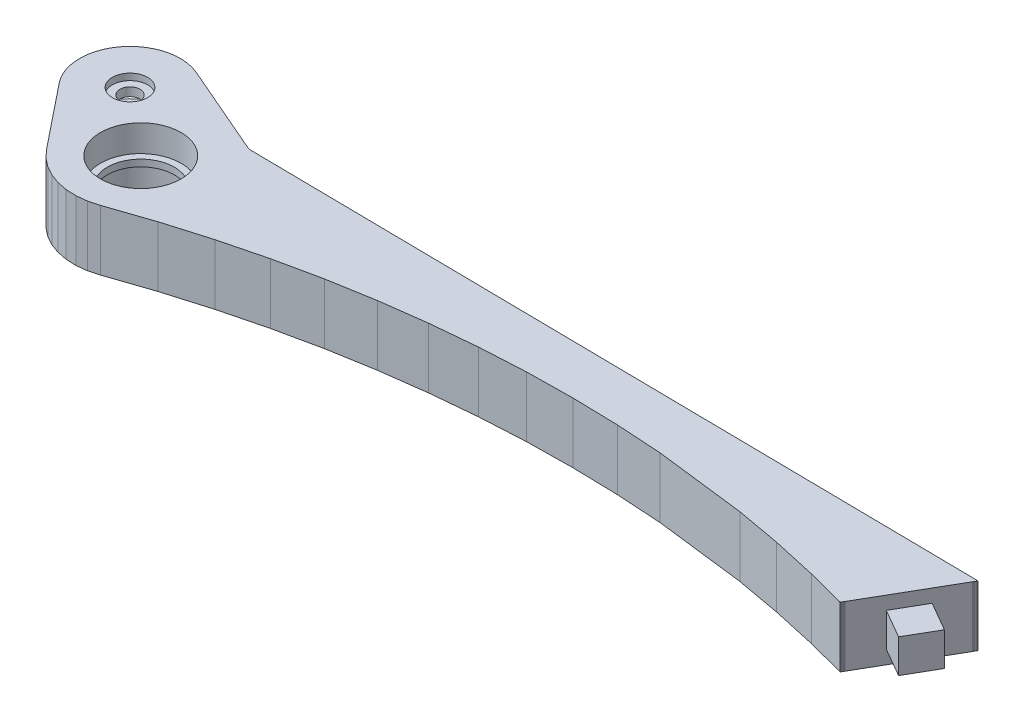
SolidWorks part; units mm, degrees
ref_plane "Спереди" through (0, 0, 0) normal (0, 0, 1) x (1, 0, 0)
ref_plane "Сверху" through (0, 0, 0) normal (0, 1, 0) x (1, 0, 0)
ref_plane "Справа" through (0, 0, 0) normal (1, 0, 0) x (0, 0, -1)
ref_plane "Плоскость4" through (0, 14.0561, 0) normal (0, 1, 0) x (1, 0, 0)
sketch "Эскиз49" plane through (0, 0, 0) normal (0, 1, 0) x (1, 0, 0)
  line L3 (268.0638, -16.9842) -> (254.1293, -41.1195)
  line L16 (268.6348, -15.9952) -> (268.6282, -16.0066)
  line L17 (268.6282, -16.0066) -> (268.6174, -16.0253)
  line L18 (268.6174, -16.0253) -> (268.6024, -16.0513)
  line L19 (268.6024, -16.0513) -> (268.5832, -16.0845)
  line L20 (268.5832, -16.0845) -> (268.5601, -16.1245)
  line L21 (268.5333, -16.171) -> (268.5601, -16.1245)
  line L22 (268.5333, -16.171) -> (268.5028, -16.2237)
  line L23 (268.5028, -16.2237) -> (268.4322, -16.3461)
  line L24 (268.4322, -16.3461) -> (268.3504, -16.4878)
  line L25 (268.3504, -16.4878) -> (268.2598, -16.6447)
  line L26 (268.1633, -16.8118) -> (268.0638, -16.9842)
  line L27 (268.2598, -16.6447) -> (268.1633, -16.8118)
  line L28 (49.2094, -13.19) -> (268.6369, -15.9915)
  line L30 (268.6369, -15.9915) -> (268.6348, -15.9952)
  line L32 (241.9488, -38.9737) -> (253.6131, -42.0136)
  line L52 (254.1293, -41.1195) -> (254.0451, -41.2654)
  line L53 (254.0451, -41.2654) -> (253.9644, -41.4052)
  line L54 (253.9644, -41.4052) -> (253.9542, -41.4228)
  line L55 (253.9542, -41.4228) -> (253.895, -41.5253)
  line L56 (253.895, -41.5253) -> (253.8783, -41.5542)
  line L57 (253.8783, -41.5542) -> (253.8101, -41.6722)
  line L58 (253.8101, -41.6722) -> (253.7988, -41.6918)
  line L59 (253.7988, -41.6918) -> (253.7643, -41.7516)
  line L60 (253.7643, -41.7516) -> (253.7404, -41.793)
  line L61 (253.7404, -41.793) -> (253.7117, -41.8427)
  line L62 (253.7117, -41.8427) -> (253.6926, -41.8759)
  line L63 (253.6926, -41.8759) -> (253.6837, -41.8913)
  line L64 (253.6837, -41.8913) -> (253.6487, -41.9519)
  line L65 (253.6487, -41.9519) -> (253.6384, -41.9698)
  line L66 (253.6384, -41.9698) -> (253.6256, -41.9918)
  line L67 (253.6256, -41.9918) -> (253.6224, -41.9975)
  line L68 (253.6224, -41.9975) -> (253.6194, -42.0025)
  line L69 (253.6194, -42.0025) -> (253.6135, -42.0129)
  line L70 (253.6135, -42.0129) -> (253.6131, -42.0136)
  line L72 (241.9488, -38.9737) -> (228.6633, -36.0268)
  line L73 (228.6633, -36.0268) -> (215.2733, -33.5987)
  line L74 (215.2733, -33.5987) -> (188.2608, -30.3122)
  line L75 (188.2608, -30.3122) -> (174.6792, -29.459)
  line L76 (174.6792, -29.459) -> (161.0746, -29.1343)
  line L77 (161.0746, -29.1343) -> (147.4673, -29.3264)
  line L78 (147.4673, -29.3264) -> (133.8791, -30.072)
  line L79 (133.8791, -30.072) -> (120.3292, -31.3329)
  line L80 (120.3292, -31.3329) -> (106.8386, -33.1197)
  line L81 (106.8386, -33.1197) -> (93.4253, -35.4174)
  line L82 (93.4253, -35.4174) -> (80.1166, -38.2588)
  line L83 (80.1166, -38.2588) -> (66.9256, -41.6035)
  line L84 (66.9256, -41.6035) -> (53.8746, -45.4585)
  line L85 (53.8746, -45.4585) -> (40.9834, -49.8179)
  line L86 (40.9834, -49.8179) -> (37.9936, -50.6387)
  line L87 (37.9936, -50.6387) -> (34.9124, -50.9724)
  line L88 (34.9124, -50.9724) -> (31.8154, -50.8562)
  line L89 (31.8154, -50.8562) -> (28.7753, -50.2476)
  line L90 (28.7753, -50.2476) -> (25.8659, -49.1765)
  line L91 (25.8659, -49.1765) -> (23.1653, -47.656)
  line L92 (23.1653, -47.656) -> (20.7238, -45.749)
  line L93 (20.7238, -45.749) -> (18.6063, -43.4875)
  line L94 (18.6063, -43.4875) -> (22.8886, -40.0603)
  line L95 (49.2094, -13.19) -> (48.8158, -13.159)
  line L96 (48.8158, -13.159) -> (48.4296, -13.0766)
  line L97 (48.4296, -13.0766) -> (48.0577, -12.9442)
  line L98 (48.0577, -12.9442) -> (30.9654, -16.8675)
  arc A0 (30.9654, -16.8675) -> (22.8886, -40.0603) centre (34.2094, -31) ccw
extrude "Бобышка-Вытянуть2" add sketch "Эскиз49" along normal blind 18 separate body
sketch "Эскиз1" plane through (0, 14.0561, 0) normal (0, 1, 0) x (1, 0, 0)
  line L0 (263.637, -24.6517) -> (258.637, -33.312)
  line L1 (258.637, -33.312) -> (267.2972, -38.312)
  line L2 (267.2972, -38.312) -> (272.2972, -29.6517)
  line L3 (272.2972, -29.6517) -> (263.637, -24.6517)
ref_plane "Плоскость5" through (0, 1.0561, 0) normal (0, 1, 0) x (1, 0, 0)
sketch "Эскиз50" plane through (0, 0, 0) normal (0, 1, 0) x (1, 0, 0)
  line L0 (18.6063, -43.4875) -> (3.3202, -24.4119)
  line L1 (18.6063, -43.4875) -> (22.8886, -40.0603)
  line L2 (48.0577, -12.9442) -> (30.9654, -16.8675) construction
  line L3 (48.0577, -12.9442) -> (30.9654, -16.8675)
  line L4 (48.0577, -12.9442) -> (20.9645, -1.2368)
  arc A0 (30.9654, -16.8675) -> (22.8886, -40.0603) centre (34.2094, -31) ccw construction
  arc A1 (30.9654, -16.8675) -> (22.8886, -40.0603) centre (34.2094, -31) ccw
  arc A2 (20.9645, -1.2368) -> (3.3202, -24.4119) centre (15.0129, -15.0099) ccw
extrude "Бобышка-Вытянуть3" add sketch "Эскиз50" along normal blind 18
sketch "Эскиз6" plane through (0, 1.0561, 0) normal (0, 1, 0) x (1, 0, 0)
  line L0 (12.5166, -19.2614) -> (12.7849, -19.4636)
  line L1 (12.7849, -19.4636) -> (13.0833, -19.618)
  line L2 (13.0833, -19.618) -> (13.8307, -19.8614)
  line L3 (13.8307, -19.8614) -> (14.607, -19.9845)
  line L4 (14.607, -19.9845) -> (15.393, -19.9845)
  line L5 (15.393, -19.9845) -> (16.1693, -19.8614)
  line L6 (16.1693, -19.8614) -> (16.9167, -19.618)
  line L7 (16.9167, -19.618) -> (17.2151, -19.4636)
  line L8 (17.2151, -19.4636) -> (17.4834, -19.2614)
  line L9 (17.4834, -19.2614) -> (17.7142, -19.0172)
  line L10 (17.7142, -19.0172) -> (17.9007, -18.7377)
  line L11 (17.9007, -18.7377) -> (18.0379, -18.431)
  line L12 (18.0379, -18.431) -> (18.1218, -18.1056)
  line L13 (18.1218, -18.1056) -> (18.15, -17.7708)
  line L14 (18.15, -17.7708) -> (18.15, -12.2292)
  line L15 (18.15, -12.2292) -> (18.1218, -11.8944)
  line L16 (18.1218, -11.8944) -> (18.0379, -11.569)
  line L17 (18.0379, -11.569) -> (17.9007, -11.2623)
  line L18 (17.9007, -11.2623) -> (17.7142, -10.9828)
  line L19 (17.7142, -10.9828) -> (17.4834, -10.7386)
  line L20 (17.4834, -10.7386) -> (17.2151, -10.5364)
  line L21 (17.2151, -10.5364) -> (16.9167, -10.382)
  line L22 (16.9167, -10.382) -> (16.1693, -10.1386)
  line L23 (16.1693, -10.1386) -> (15.393, -10.0155)
  line L24 (15.393, -10.0155) -> (14.607, -10.0155)
  line L25 (14.607, -10.0155) -> (13.8307, -10.1386)
  line L26 (13.8307, -10.1386) -> (13.0833, -10.382)
  line L27 (13.0833, -10.382) -> (12.7849, -10.5364)
  line L28 (12.7849, -10.5364) -> (12.5166, -10.7386)
  line L29 (12.5166, -10.7386) -> (12.2858, -10.9828)
  line L30 (12.2858, -10.9828) -> (12.0993, -11.2623)
  line L31 (12.0993, -11.2623) -> (11.9621, -11.569)
  line L32 (11.9621, -11.569) -> (11.8782, -11.8944)
  line L33 (11.8782, -11.8944) -> (11.85, -12.2292)
  line L34 (11.85, -12.2292) -> (11.85, -17.7708)
  line L35 (11.85, -17.7708) -> (11.8782, -18.1056)
  line L36 (11.8782, -18.1056) -> (11.9621, -18.431)
  line L37 (11.9621, -18.431) -> (12.0993, -18.7377)
  line L38 (12.0993, -18.7377) -> (12.2858, -19.0172)
  line L39 (12.2858, -19.0172) -> (12.5166, -19.2614)
extrude "Вырез-Вытянуть1" cut sketch "Эскиз6" against normal through all
extrude "Вырез-Вытянуть8" cut sketch "Эскиз50<3>" along normal blind 9 from offset 4.5
sketch "Эскиз50<3>" plane through (0, 0, 0) normal (0, 1, 0) x (1, 0, 0) same geometry as "Эскиз50"
ref_plane "Плоскость6" through (0, 4.5561, 0) normal (0, 1, 0) x (1, 0, 0)
sketch "Эскиз12" plane through (0, 4.5561, 0) normal (0, 1, 0) x (1, 0, 0)
  circle A0 centre (15, -15) radius 3
extrude "Вырез-Вытянуть2" cut sketch "Эскиз12" against normal through all
ref_plane "Плоскость7" through (0, 16.0561, 0) normal (0, -1, 0) x (-1, 0, 0)
sketch "Эскиз19" plane through (0, 16.0561, 0) normal (0, -1, 0) x (-1, 0, 0)
  circle A0 centre (-15, -15) radius 5.25
extrude "Вырез-Вытянуть3" cut sketch "Эскиз19" against normal through all
ref_plane "Плоскость8" through (0, 8.0561, 0) normal (0, 1, 0) x (1, 0, 0)
sketch "Эскиз28" plane through (0, 8.0561, 0) normal (0, 1, 0) x (1, 0, 0)
  circle A0 centre (34.2094, -31) radius 12
extrude "Вырез-Вытянуть5" cut sketch "Эскиз28" against normal through all
ref_plane "Плоскость9" through (0, 10.0561, 0) normal (0, 1, 0) x (1, 0, 0)
sketch "Эскиз37" plane through (0, 10.0561, 0) normal (0, 1, 0) x (1, 0, 0)
  circle A0 centre (34.2094, -31) radius 10
extrude "Вырез-Вытянуть6" cut sketch "Эскиз37" against normal through all
ref_plane "Плоскость10" through (0, 10.0561, 0) normal (0, -1, 0) x (-1, 0, 0)
sketch "Эскиз47" plane through (0, 10.0561, 0) normal (0, -1, 0) x (-1, 0, 0)
  circle A0 centre (-34.2094, -31) radius 12
extrude "Вырез-Вытянуть7" cut sketch "Эскиз47" against normal through all
extrude "Бобышка-Вытянуть4" add sketch "Эскиз1" against normal blind 10 separate body
sketch "Эскиз51" plane through (0, 16.0561, 0) normal (0, 1, 0) x (1, 0, 0)
  circle A0 centre (15, -15) radius 3
extrude "Вырез-Вытянуть9" cut sketch "Эскиз51" against normal blind 5
